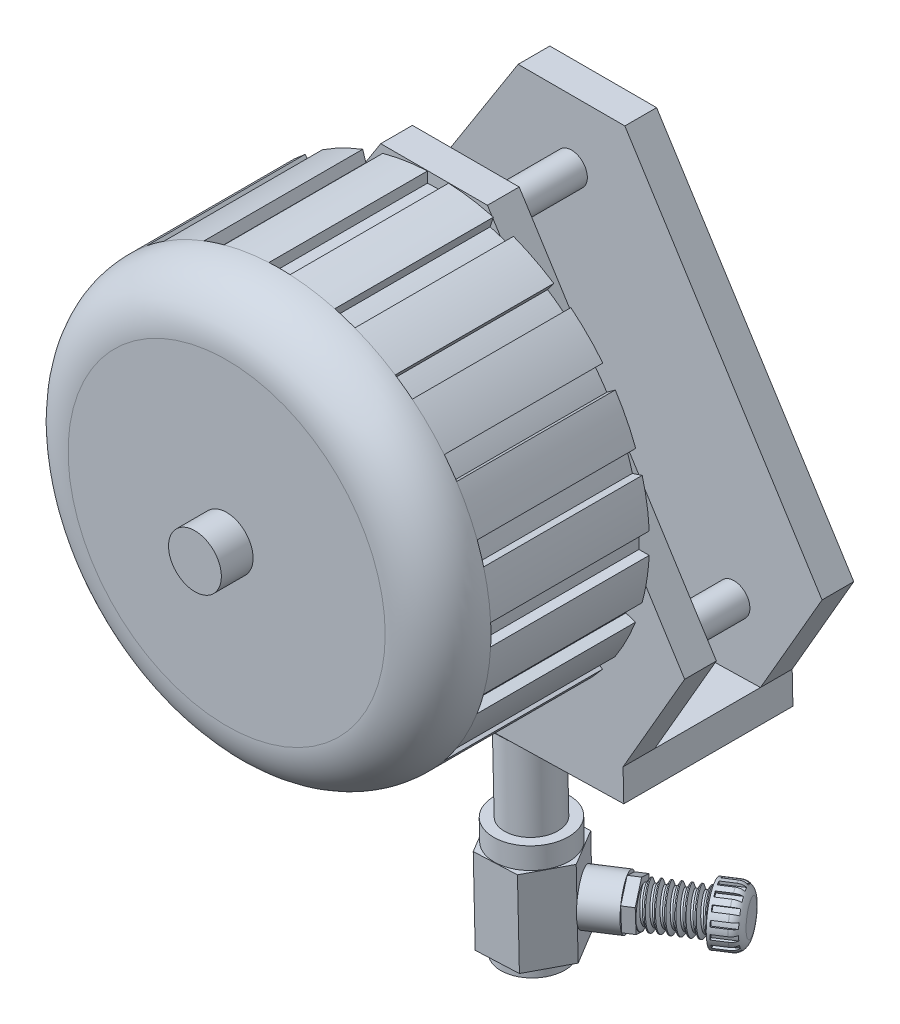
SolidWorks part; units mm, degrees
ref_plane "Front Plane" through (0, 0, 0) normal (0, 0, 1) x (1, 0, 0)
ref_plane "Top Plane" through (0, 0, 0) normal (0, 1, 0) x (1, 0, 0)
ref_plane "Right Plane" through (0, 0, 0) normal (1, 0, 0) x (0, 0, -1)
sketch "Sketch1" plane through (0, 0, 0) normal (0, 0, 1) x (1, 0, 0)
  circle A0 centre (0, 0) radius 20
  dimension "D1" = 40
extrude "Boss-Extrude1" add sketch "Sketch1" along normal blind 20
fillet "Fillet1" radius 5 1 edges at (20, 0, 20)
sketch "Sketch2" plane through (0, 0, 20) normal (0, 0, 1) x (1, 0, 0)
  circle A0 centre (0, 0) radius 2.5
  dimension "D1" = 5
extrude "Boss-Extrude2" add sketch "Sketch2" along normal blind 3
sketch "Sketch3" plane through (0, 0, 0) normal (0, 0, -1) x (-1, 0, 0)
  line L1 (0, 20.3338) -> (-1, 20.3338)
  line L2 (0, 20.3338) -> (1, 20.3338)
  line L3 (1, 20.3338) -> (1, 18.9737)
  line L4 (-1, 20.3338) -> (-1, 18.9737)
  arc A0 (1, 18.9737) -> (-1, 18.9737) centre (0, 0) ccw
  dimension "D1" = 38
extrude "Cut-Extrude2" cut sketch "Sketch3" against normal blind 15
pattern_circular "CirPattern1" count 20 over 360 about axis through (0, -0.0311, 0) along (0, 0, 1) of "Cut-Extrude2"
sketch "Sketch5" plane through (0, 0, 0) normal (0, 0, -1) x (-1, 0, 0)
  line L1 (0, 20) -> (5.4258, 20)
  line L2 (5.4258, 20) -> (-4.6715, 20)
  line L4 (-4.6715, 20) -> (-23.326, -9.5071)
  line L6 (0, -20) -> (-17.4999, -19.5923)
  line L7 (0, -20) -> (17.4953, -20.4076)
  line L8 (-17.4999, -19.5923) -> (-23.326, -9.5071)
  line L9 (5.4258, 20) -> (24.2494, -9.5071)
  line L10 (24.2494, -9.5071) -> (17.4953, -20.4076)
  arc A0 (1, 19.975) -> (-1, 19.975) centre (0, 0) ccw construction
  arc A1 (-1, -19.975) -> (1, -19.975) centre (0, 0) ccw construction
  dimension "D1" = 121.349
extrude "Boss-Extrude3" add sketch "Sketch5" along normal blind 3 contours L10 L9 L1 L2 L4 L8 L6 L7
sketch "Sketch6" plane through (0, 0, -3) normal (0, 0, -1) x (-1, 0, 0)
  circle A0 centre (-14.9999, -13.5923) radius 1.5
  circle A1 centre (14.9953, -14.4076) radius 1.5
  circle A2 centre (0.3772, 14) radius 1.5
  dimension "D1" = 3
  dimension "D2" = 3
  dimension "D3" = 3
extrude "Boss-Extrude4" add sketch "Sketch6" along normal blind 10
sketch "Sketch7" plane through (0, 0, -13) normal (0, 0, -1) x (-1, 0, 0)
  line L0 (-17.4999, -19.5923) -> (-23.326, -9.5071)
  line L1 (-23.326, -9.5071) -> (-4.6715, 20)
  line L2 (-4.6715, 20) -> (5.4258, 20)
  line L3 (5.4258, 20) -> (24.2494, -9.5071)
  line L4 (24.2494, -9.5071) -> (17.4953, -20.4076)
  line L5 (17.4953, -20.4076) -> (-17.4999, -19.5923) construction
  line L6 (17.4953, -20.4076) -> (-17.4999, -19.5923)
extrude "Boss-Extrude5" add sketch "Sketch7" along normal blind 3
sketch "Sketch9" plane through (0, 0, -16) normal (0, 0, -1) x (-1, 0, 0)
  circle A0 centre (0, 0) radius 5
  circle A1 centre (0, 0) radius 7.5
  dimension "D1" = 10
  dimension "D2" = 15
extrude "Boss-Extrude6" add sketch "Sketch9" along normal blind 5
sketch "Sketch10" plane through (0.4657, -19.9892, 0) normal (0.0233, -0.9997, 0) x (0.9997, 0.0233, 0)
  line L0 (-16.9847, 0) -> (-18.8393, 0) construction
  line L1 (-17.912, 0) -> (17.0389, 0)
  line L2 (-17.912, 0) -> (-17.912, -16)
  line L3 (-17.912, -16) -> (17.0389, -16)
  line L4 (17.0389, 0) -> (17.0389, -16)
extrude "Boss-Extrude7" add sketch "Sketch10" along normal blind 3
sketch "Sketch11" plane through (0.5356, -22.9883, 0) normal (0.0233, -0.9997, 0) x (0.9997, 0.0233, 0)
  line L1 (2.9628, -3.0447) -> (-2.81, -2.9565)
  line L2 (-2.81, -2.9565) -> (-5.7728, -7.9118)
  line L3 (-5.7728, -7.9118) -> (-2.9628, -12.9553)
  line L4 (-2.9628, -12.9553) -> (2.81, -13.0435)
  line L5 (2.81, -13.0435) -> (5.7728, -8.0882)
  line L6 (5.7728, -8.0882) -> (2.9628, -3.0447)
  circle A0 centre (0, -8) radius 5 construction
  dimension "D1" = 10
extrude "Boss-Extrude8" add sketch "Sketch11" along normal blind 3
sketch "Sketch13" plane through (-17.9071, -0.4172, 0) normal (-0.9997, -0.0233, 0) x (0, 0, 1)
  line L0 (-16, -21.4946) -> (0, -21.4946)
  line L1 (-16, -22.9946) -> (-16, -19.9946) construction
  line L2 (0, -22.9946) -> (0, -19.9946) construction
ref_plane "Plane1" through (0.5006, -21.4887, 0) normal (0.0233, -0.9997, 0) x (-0.9997, -0.0233, 0)
mirror "Mirror1" about plane through (0.5006, -21.4887, 0) normal (0.0233, -0.9997, 0) of "Boss-Extrude8"
sketch "Sketch14" plane through (0.6054, -25.9875, 0) normal (0.0233, -0.9997, 0) x (0.9997, 0.0233, 0)
  circle A0 centre (0, -8) radius 2.5
  dimension "D1" = 5
extrude "Boss-Extrude9" add sketch "Sketch14" along normal blind 10
sketch "Sketch15" plane through (0.8383, -35.9848, 0) normal (0.0233, -0.9997, 0) x (-0.9997, -0.0233, 0)
  circle A0 centre (0, 8) radius 3.5
  dimension "D1" = 7
extrude "Boss-Extrude10" add sketch "Sketch15" along normal blind 2
sketch "Sketch16" plane through (0.8849, -37.9843, 0) normal (0.0233, -0.9997, 0) x (-0.9997, -0.0233, 0)
  line L1 (-2.1249, 4.5) -> (1.9686, 4.4097)
  line L2 (1.9686, 4.4097) -> (4.0936, 7.9097)
  line L3 (4.0936, 7.9097) -> (2.1249, 11.5)
  line L4 (2.1249, 11.5) -> (-1.9686, 11.5903)
  line L5 (-1.9686, 11.5903) -> (-4.0936, 8.0903)
  line L6 (-4.0936, 8.0903) -> (-2.1249, 4.5)
  circle A0 centre (0, 8) radius 3.546 construction
extrude "Boss-Extrude11" add sketch "Sketch16" along normal blind 8
sketch "Sketch17" plane through (1.0713, -45.9821, 0) normal (0.0233, -0.9997, 0) x (0.9997, 0.0233, 0)
  circle A0 centre (0, -7.9097) radius 3
  circle A1 centre (0, -7.9097) radius 2.5
  dimension "D1" = 5
  dimension "D2" = 6
extrude "Boss-Extrude12" add sketch "Sketch17" along normal blind 1
sketch "Sketch18" plane through (6.5782, 0.1533, -3.9949) normal (0.8546, 0.0199, -0.519) x (-0.5188, -0.0121, -0.8548)
  circle A0 centre (6.8384, -41.9946) radius 2.25
  dimension "D1" = 4.5
extrude "Boss-Extrude13" add sketch "Sketch18" along normal blind 3
sketch "Sketch19" plane through (9.1419, 0.213, -5.5518) normal (0.8546, 0.0199, -0.519) x (-0.5188, -0.0121, -0.8548)
  line L1 (8.7352, -40.7844) -> (6.7388, -39.7468)
  line L2 (6.7388, -39.7468) -> (4.8419, -40.9569)
  line L3 (4.8419, -40.9569) -> (4.9415, -43.2047)
  line L4 (4.9415, -43.2047) -> (6.9379, -44.2424)
  line L5 (6.9379, -44.2424) -> (8.8348, -43.0322)
  line L6 (8.8348, -43.0322) -> (8.7352, -40.7844)
  circle A0 centre (6.8384, -41.9946) radius 1.9486 construction
extrude "Boss-Extrude14" add sketch "Sketch19" along normal blind 1
sketch "Sketch20" plane through (9.9964, 0.2329, -6.0707) normal (0.8546, 0.0199, -0.519) x (-0.5188, -0.0121, -0.8548)
  circle A0 centre (6.8384, -41.9946) radius 1.5
extrude "Boss-Extrude15" add sketch "Sketch20" along normal blind 5
thread "Thread1" pitch 0.7 start angle 0, offset 5, length 10, pitch 0.7, diameter 3
ref_plane "Plane2" through (16.7505, -41.6157, -15.8236) normal (0.0233, -0.9997, 0) x (0.5188, 0.0121, 0.8548)
sketch "Thread Profile1" plane through (16.7505, -41.6157, -15.8236) normal (0.0233, -0.9997, 0) x (0.5188, 0.0121, 0.8548)
  line L0 (0, 0) -> (0, 0.7) construction
  line L1 (0, 0) -> (0.3789, 0.2187)
  line L2 (0.3789, 0.2187) -> (0.3789, 0.3062)
  line L3 (0.3789, 0.3062) -> (0, 0.525)
  line L4 (0.3789, 0.2625) -> (0, 0.2625) construction
  line L11 (0, 0) -> (0, 0.525)
  point P2 (0, 0)
  dimension "Pitch" = 0.7
  dimension "Profile_Angle" = 60
  dimension "Profile_Land" = 0.0875
  dimension "Profile_Height" = 0.3789
sketch "Sketch26" plane through (14.2692, 0.3324, -8.6656) normal (0.8546, 0.0199, -0.519) x (-0.5188, -0.0121, -0.8548)
  line L1 (0.873, -46.7093) -> (12.8037, -46.7093)
  line L2 (0.873, -46.7093) -> (0.873, -36.9619)
  line L3 (0.873, -36.9619) -> (12.8037, -36.9619)
  line L4 (12.8037, -46.7093) -> (12.8037, -36.9619)
  line L5 (0.873, -46.7093) -> (12.8037, -36.9619) construction
  line L6 (0.873, -36.9619) -> (12.8037, -46.7093) construction
  point P0 (6.8384, -41.8356)
extrude "Cut-Extrude3" cut sketch "Sketch26" along normal blind 10
sketch "Sketch27" plane through (14.2692, 0.3324, -8.6656) normal (0.8546, 0.0199, -0.519) x (-0.5188, -0.0121, -0.8548)
  circle A0 centre (6.8384, -41.9946) radius 2.5
  dimension "D1" = 5
extrude "Boss-Extrude16" add sketch "Sketch27" along normal blind 2.5
fillet "Fillet3" radius 1 1 edges at (12.5381, -41.6836, -17.9452)
sketch "Sketch28" plane through (16.4057, 0.3822, -9.963) normal (0.8546, 0.0199, -0.519) x (-0.5188, -0.0121, -0.8548)
  line L1 (6.8384, -39.4095) -> (7.0679, -39.4095)
  line L2 (6.8384, -39.4095) -> (6.5884, -39.4095)
  line L3 (6.5884, -39.4095) -> (6.5884, -39.7585)
  line L4 (7.0679, -39.4095) -> (7.0679, -39.7563)
  arc A0 (7.0679, -39.7563) -> (6.5884, -39.7585) centre (6.8384, -41.9946) ccw
  dimension "D1" = 4.5
extrude "Cut-Extrude4" cut sketch "Sketch28" against normal blind 2.25
pattern_circular "CirPattern2" count 15 over 360 about axis through (-2.5698, -42.0658, -5.8454) along (0.8546, 0.0199, -0.519) of "Cut-Extrude4"
